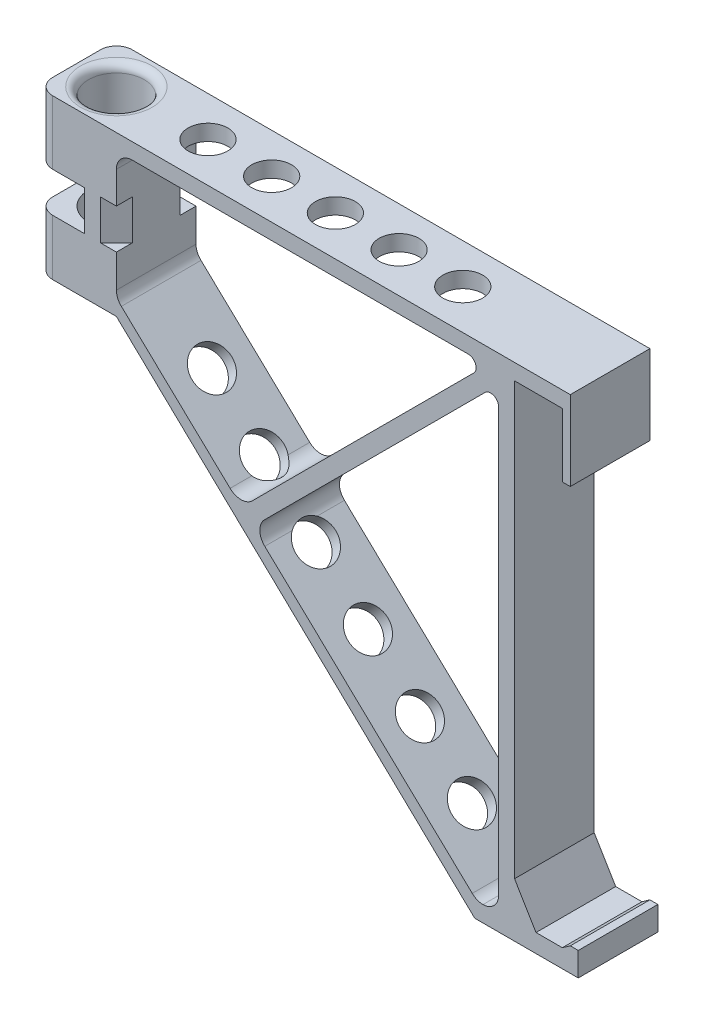
SolidWorks part; units mm, degrees
ref_plane "Front Plane" through (0, 0, 0) normal (0, 0, 1) x (1, 0, 0)
ref_plane "Top Plane" through (0, 0, 0) normal (0, 1, 0) x (1, 0, 0)
ref_plane "Right Plane" through (0, 0, 0) normal (1, 0, 0) x (0, 0, -1)
sketch "Sketch1" plane through (0, 0, 0) normal (0, 0, 1) x (1, 0, 0)
  line L0 (-8, 44.65) -> (-8, 60.65)
  line L1 (-8, 62.65) -> (49, 62.65)
  line L2 (49, 62.65) -> (49, 52.65)
  line L3 (49, 52.65) -> (48, 52.65)
  line L4 (48, 52.65) -> (48, 60.65)
  line L5 (48, 60.65) -> (42, 60.65)
  line L6 (42, 60.65) -> (42, 6.5)
  line L7 (37, -0.2965) -> (50, -0.2965)
  line L8 (-8, 42.65) -> (37, -0.2965)
  line L9 (50, -0.2965) -> (50, 2.7035)
  line L10 (50, 2.7035) -> (49, 2.7035)
  line L11 (49, 2.7035) -> (48, 2)
  line L12 (48, 2) -> (44.7, 2)
  line L13 (44.7, 2) -> (42, 6.5)
  line L14 (-8, 42.65) -> (-18, 42.65)
  line L15 (-18, 42.65) -> (-18, 62.65)
  line L16 (-18, 62.65) -> (-8, 62.65)
  line L17 (-8, 60.65) -> (38.5858, 60.65)
  line L18 (40, 59.2358) -> (40, 1.7035)
  line L19 (40, 1.7035) -> (37.268, 1.7035)
  line L20 (37.268, 1.7035) -> (9.1468, 28.3826)
  line L21 (40, 60.65) -> (8.4211, 29.0711) construction
  line L22 (38.5858, 60.65) -> (7.6954, 29.7596)
  line L23 (9.1468, 28.3826) -> (40, 59.2358)
  line L24 (7.6954, 29.7596) -> (-8, 44.65)
  dimension "D1" = 1
  dimension "D2" = 10
  dimension "D3" = 2
  dimension "D4" = 5
  dimension "D5" = 8
  dimension "D6" = 6
  dimension "D7" = 54.15
  dimension "D8" = 4.5
  dimension "D9" = 2.7
  dimension "D10" = 3.3
  dimension "D11" = 3
  dimension "D12" = 1
  dimension "D13" = 50
  dimension "D14" = 58.65
  dimension "D15" = 20
  dimension "D16" = 10
  dimension "D17" = 2
  dimension "D18" = 2
  dimension "D19" = 2
  dimension "D20" = 1
  dimension "D21" = 2
extrude "Frame" add sketch "Sketch1" along normal blind 10
sketch "Sketch13" plane through (0, 42.65, 0) normal (0, -1, 0) x (1, 0, 0)
  line L0 (-18, 0) -> (-8, 0) construction
  line L1 (-18, 10) -> (-18, 0) construction
  circle A0 centre (-13, 5) radius 3.5
  point P2 (-13, 0)
  dimension "D1" = 7
  dimension "D2" = 5
  dimension "D3" = 5
extrude "Cut-Extrude7" cut sketch "Sketch13" against normal through all
fillet "Fillet4" radius 1 2 edges at (-13, 62.65, 1.5) (-13, 42.65, 1.5)
sketch "Sketch14" plane through (0, 0, 10) normal (0, 0, 1) x (1, 0, 0)
  line L0 (-18, 62.65) -> (-18, 42.65) construction
  line L1 (-18, 54.65) -> (-13, 54.65)
  line L2 (-18, 54.65) -> (-18, 49.65)
  line L3 (-18, 49.65) -> (-13, 49.65)
  line L4 (-13, 54.65) -> (-13, 49.65)
  line L5 (-18, 42.65) -> (-8, 42.65) construction
  dimension "D1" = 5
  dimension "D2" = 7
  dimension "D3" = 5
extrude "Cut-Extrude8" cut sketch "Sketch14" against normal through all
fillet "Fillet5" radius 2 4 edges at (-18, 46.15, 0) (-18, 58.65, 0) (-18, 46.15, 10) (-18, 58.65, 10)
ref_plane "Plane1" through (0, 49.65, 0) normal (0, 1, 0) x (1, 0, 0)
sketch "Sketch15" plane through (0, 49.65, 0) normal (0, 1, 0) x (1, 0, 0)
  line L0 (-10, 0) -> (-8, -2)
  line L1 (49, 0) -> (-16, 0) construction
  line L2 (-8, -10) -> (-8, 0) construction
  line L3 (-8, -2) -> (-8, 0)
  line L4 (-8, 0) -> (-10, 0)
  line L5 (-10, -10) -> (-8, -8)
  line L6 (49, -10) -> (-16, -10) construction
  line L7 (-8, -8) -> (-8, -10)
  line L8 (-8, -10) -> (-10, -10)
  dimension "D1" = 2
  dimension "D2" = 2
  dimension "D3" = 2
  dimension "D4" = 2
extrude "Cut-Extrude9" cut sketch "Sketch15" along normal blind 5
chamfer "Chamfer1" distance 1 angle 45 2 edges at (-13, 52.15, 10) (-13, 52.15, 0)
fillet "Fillet6" radius 2 6 edges at (-8, 60.65, 5) (40, 1.7035, 5) (37.268, 1.7035, 5) (-8, 44.65, 5) (9.1468, 28.3826, 5) (7.6954, 29.7596, 5)
fillet "Fillet7" radius 1 2 edges at (40, 59.2358, 5) (38.5858, 60.65, 5)
sketch "Sketch18" plane through (17.4885, 18.3247, 0) normal (-0.6904, -0.7234, 0) x (0.7234, -0.6904, 0)
  line L0 (-35.2333, 10) -> (26.9712, 10) construction
  circle A0 centre (-26.969, 5) radius 2.5
  circle A1 centre (-17.969, 5) radius 2.5
  circle A2 centre (-8.969, 5) radius 2.5
  circle A3 centre (0.031, 5) radius 2.5
  circle A4 centre (9.031, 5) radius 2.5
  circle A5 centre (18.031, 5) radius 2.5
  dimension "D2" = 5
  dimension "D1" = 5
  dimension "D3" = 6
extrude "Cut-Extrude11" cut sketch "Sketch18" against normal up to next
sketch "Sketch19" plane through (0, 62.65, 0) normal (0, 1, 0) x (1, 0, 0)
  line L0 (49, 0) -> (-16, 0) construction
  circle A0 centre (-1.5, -5) radius 2.5
  arc A1 (-13, -1.5) -> (-13, -8.5) centre (-13, -5) ccw construction
  circle A2 centre (6.5, -5) radius 2.5
  circle A3 centre (14.5, -5) radius 2.5
  circle A4 centre (22.5, -5) radius 2.5
  circle A5 centre (30.5, -5) radius 2.5
  point P6 (-16.5, -5)
  dimension "D2" = 5
  dimension "D1" = 5
  dimension "D3" = 15
  dimension "D4" = 5
extrude "Cut-Extrude12" cut sketch "Sketch19" against normal up to next
sketch "Sketch17" plane through (0, 0, 10) normal (0, 0, 1) x (1, 0, 0)
  line L0 (49, 62.65) -> (-16, 62.65) construction
  line L1 (34, 62.65) -> (42.0673, 62.65)
  line L2 (42.0673, 62.65) -> (42, 49.3835)
  line L3 (42, 6.5) -> (42, 60.65) construction
  line L4 (37, -0.2965) -> (50, -0.2965) construction
  line L5 (29.4949, 6.8661) -> (37, -0.2965)
  line L6 (-8, 42.65) -> (37, -0.2965) construction
  line L7 (37, -0.2965) -> (42, -0.2965)
  line L8 (42, -0.2965) -> (42, 15.3622)
  line L9 (-2.0671, 62.65) -> (-10.5875, 62.65)
  line L11 (-8, 42.65) -> (-4.2532, 39.0742)
  line L12 (-10.5875, 62.65) -> (-10.5875, 42.65)
  line L13 (-16, 42.65) -> (-8, 42.65) construction
  line L14 (-10.5875, 42.65) -> (-8, 42.65)
  arc A0 (-2.0671, 62.65) -> (-4.2532, 39.0742) centre (-17.5426, 52.1957) ccw
  arc A1 (42, 49.3835) -> (34, 62.65) centre (49, 62.65) ccw
  arc A2 (29.4949, 6.8661) -> (42, 15.3622) centre (43.5, -0.2965) ccw
  dimension "D3" = 30
extrude "ears" [suppressed] add sketch "Sketch17" against normal blind 0.4 separate body
